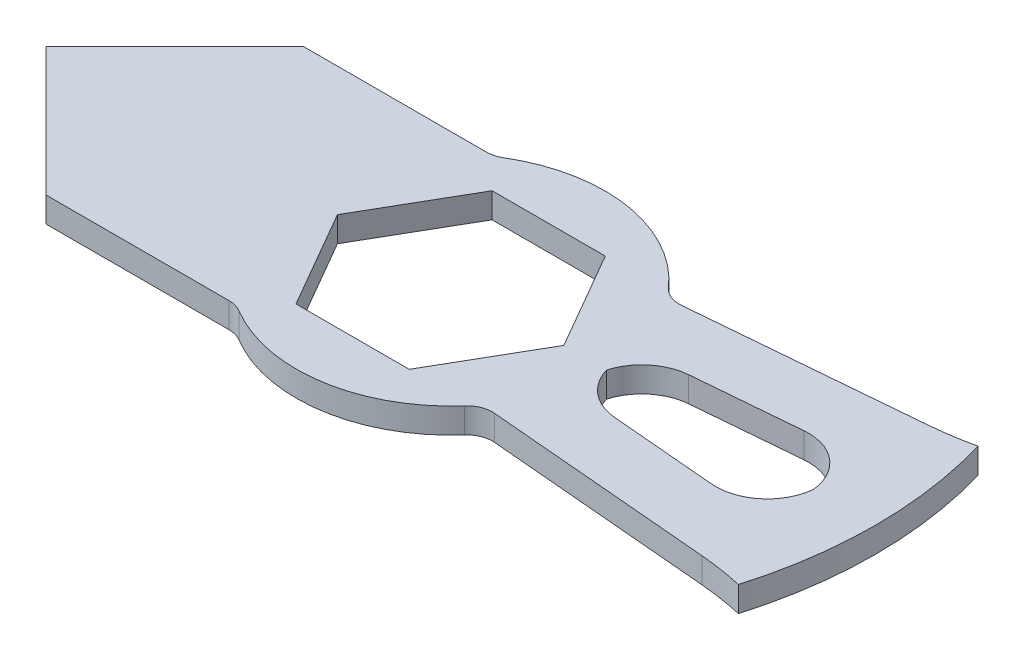
SolidWorks part; units mm, degrees
ref_plane "Front Plane" through (0, 0, 0) normal (0, 0, 1) x (1, 0, 0)
ref_plane "Top Plane" through (0, 0, 0) normal (0, 1, 0) x (1, 0, 0)
ref_plane "Right Plane" through (0, 0, 0) normal (1, 0, 0) x (0, 0, -1)
other "Center of Mass"
sketch "Sketch1" plane through (0, 0, 0) normal (0, 1, 0) x (1, 0, 0)
  line L0 (-82.55, 0) -> (82.55, 0) construction
  line L1 (0, -82.55) -> (0, 82.55) construction
  line L24 (70.7731, 21.9718) -> (24.0453, 17.9395)
  line L33 (69.8592, 9.8483) -> (29.3202, 6.3501)
  line L38 (69.8592, -9.8483) -> (29.3202, -6.3501)
  line L39 (-78.6331, 0) -> (-53.6331, 25)
  line L40 (69.8592, -9.8483) -> (17.2007, -5.3042) construction
  line L41 (69.8592, 9.8483) -> (17.2007, 5.3042) construction
  line L42 (-62.037, -13) -> (-62.037, 13) construction
  line L43 (-78.6331, 0) -> (-53.6331, -25)
  line L44 (70.7731, -21.9718) -> (24.0453, -17.9395)
  line L46 (-74.037, 25) -> (-16.5831, 25) construction
  line L47 (-74.037, -25) -> (-74.037, 25) construction
  line L48 (-74.037, -25) -> (-16.5831, -25) construction
  line L51 (-53.6331, 25) -> (-16.5831, 25)
  line L52 (-53.6331, -25) -> (-16.5831, -25)
  line L55 (-62.037, 13) -> (-12.4499, 13) construction
  line L56 (-62.037, -13) -> (-12.4499, -13) construction
  circle A0 centre (0, 0) radius 82.55 construction
  circle A6 centre (0, 0) radius 0.0381
  arc A26 (79.2, 23.278) -> (70.7731, 21.9718) centre (65.3538, 84.7726) cw
  arc A44 (69.8592, -9.8483) -> (69.8592, -9.8483) centre (69.8592, -9.8483) cw
  arc A46 (69.8592, -9.8483) -> (69.8592, 9.8483) centre (0, 0) ccw
  arc A48 (69.8592, 9.8483) -> (69.8592, 9.8483) centre (69.8592, 9.8483) ccw
  arc A49 (79.2, -23.278) -> (70.7731, -21.9718) centre (65.3538, -84.7726) ccw
  arc A51 (-12.4499, -13) -> (17.2007, -5.3042) centre (0, 0) ccw construction
  arc A56 (79.2, -23.278) -> (79.2, 23.278) centre (0, 0) ccw
  arc A59 (24.0453, 17.9395) -> (-16.5831, 25) centre (0, 0) ccw
  arc A62 (29.3202, -6.3501) -> (29.3202, 6.3501) centre (0, 0) ccw
  arc A63 (-16.5831, -25) -> (24.0453, -17.9395) centre (0, 0) ccw
  arc A65 (17.2007, 5.3042) -> (-12.4499, 13) centre (0, 0) ccw construction
  point P6 (0, 0)
  point P10 (0, 0)
  point P11 (-20.2018, 14.7271)
  point P12 (14.4373, 20.4099)
  point P13 (78.3727, 25.9271)
  point P14 (-51.1, 37.2518)
  point P16 (-51.1, -37.2518)
  point P17 (14.4373, -20.4099)
  point P18 (78.3727, -25.9271)
  point P19 (73.26, -18.4599)
  point P20 (73.26, 18.4599)
  point P21 (12.2435, 13.1946)
  point P22 (0, 0)
  point P23 (-17.5239, 4.1123)
  point P24 (-49.2137, 27.214)
  point P25 (0, 0)
  point P26 (-49.2137, -27.214)
  point P27 (-17.5239, -4.1123)
  point P28 (0, 0)
  point P29 (12.2435, -13.1946)
  point P31 (71.3749, 14.9977)
  point P33 (20.4118, 10.5999)
  point P35 (80.1685, -21.4504)
  point P36 (65.5954, -84.7935)
  point P40 (-73.2494, 3.8)
  point P41 (-73.2494, -3.8)
  point P45 (-26.6376, 13.8)
  point P47 (80.1685, 21.4504)
  point P48 (-26.6376, -13.8)
  point P55 (87.0841, -25.5352)
  point P56 (71.0147, -21.9926)
  point P58 (86.8425, 25.5143)
  point P61 (-66.2494, 3.8)
  point P62 (-66.2494, -3.8)
  point P67 (-21.9718, -6.8)
  point P68 (0, 0)
  point P70 (20.4118, -10.5999)
  point P73 (71.6165, -15.0186)
  point P77 (74.4285, -15.3185)
  point P78 (0, 0)
  point P79 (74.4265, 15.3286)
  dimension "D1" = 165.1
  dimension "D2" = 30
  dimension "D5" = 0.0762
  dimension "D4" = 4.932
  dimension "D3" = 12
  dimension "D8" = 63.0342
  dimension "D7" = 25
  dimension "D9" = 46.9015
  dimension "D6" = 62.05
  dimension "D10" = 135
  dimension "D11" = 17.9395
extrude "Boss-Extrude1" add sketch "Sketch1" along normal blind 4.9 contours A49 A56 A26 L24 L44 A6 region at (-0.6914, 0, 0)
sketch "Sketch3" plane through (0, 4.9, 0) normal (0, 1, 0) x (1, 0, 0)
  line L1 (22, 0) -> (11, 19.0526)
  line L2 (11, 19.0526) -> (-11, 19.0526)
  line L3 (-11, 19.0526) -> (-22, 0)
  line L4 (-22, 0) -> (-11, -19.0526)
  line L5 (-11, -19.0526) -> (11, -19.0526)
  line L6 (11, -19.0526) -> (22, 0)
  circle A1 centre (0, 0) radius 19.0526 construction
  dimension "D1" = 22
extrude "Cut-Extrude3" cut sketch "Sketch3" against normal blind 10
fillet "Fillet4" radius 5 4 edges at (24.0453, 2.45, 17.9395) (-16.5831, 2.45, 25) (-16.5831, 2.45, -25) (24.0453, 2.45, -17.9395)
fillet "Fillet5" radius 10 4 edges at (69.8592, 2.45, 9.8483) (69.8592, 2.45, -9.8483) (29.3202, 2.45, 6.3501) (29.3202, 2.45, -6.3501)
